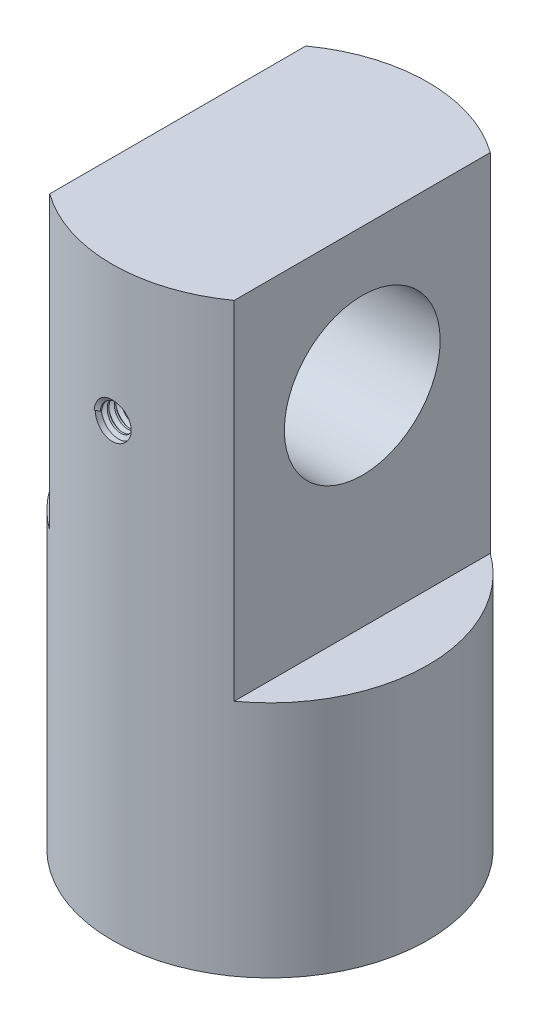
SolidWorks part; units mm, degrees
ref_plane "Front Plane" through (0, 0, 0) normal (0, 0, 1) x (1, 0, 0)
ref_plane "Top Plane" through (0, 0, 0) normal (0, 1, 0) x (1, 0, 0)
ref_plane "Right Plane" through (0, 0, 0) normal (1, 0, 0) x (0, 0, -1)
sketch "Sketch1" plane through (0, 0, 0) normal (0, 1, 0) x (1, 0, 0)
  circle A0 centre (0, 0) radius 22.32
  dimension "D1" = 44.64
extrude "Boss-Extrude1" add sketch "Sketch1" against normal blind 82.8
ref_plane "Plane1" through (0, -82.8, 0) normal (0, -1, 0) x (-1, 0, 0)
sketch "Sketch2" plane through (0, 0, 0) normal (0, 1, 0) x (1, 0, 0)
  line L2 (-13.05, 18.1075) -> (-13.05, -18.1075) construction
  line L4 (13.05, 18.1075) -> (13.05, -18.1075) construction
  circle A0 centre (0, 0) radius 22.32 construction
  arc A1 (-13.05, -18.1075) -> (13.05, -18.1075) centre (0, 0) ccw construction
  arc A2 (-13.05, 18.1075) -> (13.05, 18.1075) centre (0, 0) cw construction
  dimension "D3" = 22.32
  dimension "D4" = 22.32
  dimension "D1" = 26.1
  dimension "D2" = 36.2149
  dimension "D5" = 36.2149
sketch "Sketch3" plane through (0, 0, 0) normal (0, 1, 0) x (1, 0, 0)
  line L0 (-13.05, 18.1075) -> (-13.05, -18.1075)
  arc A0 (-13.05, 18.1075) -> (-13.05, -18.1075) centre (0, 0) ccw
  circle A1 centre (0, 0) radius 22.32 construction
extrude "Cut-Extrude1" cut sketch "Sketch3" against normal blind 41.26
sketch "Sketch4" plane through (0, 0, 0) normal (0, 1, 0) x (1, 0, 0)
  line L0 (13.05, 18.1075) -> (13.05, -18.1075)
  arc A0 (13.05, 18.1075) -> (13.05, -18.1075) centre (0, 0) cw
extrude "Cut-Extrude2" cut sketch "Sketch4" against normal blind 49.1
sketch "Sketch5" plane through (0, 0, 0) normal (1, 0, 0) x (0, 0, -1)
  line L0 (-18.1075, 0) -> (18.1075, 0) construction
  circle A0 centre (0, -19.47) radius 11.02
  dimension "D1" = 22.04
  dimension "D2" = 19.47
extrude "Cut-Extrude3" cut sketch "Sketch5" against normal through all both and the other way through all
sketch "Sketch6" plane through (0, -82.8, 0) normal (0, -1, 0) x (-1, 0, 0)
  circle A0 centre (0, 0) radius 10.15
  dimension "D1" = 20.3
hole_wizard "Ø20.0mm Dowel Hole1" positions "Sketch7" profile "Sketch8" hole size "Ø20.0" standard "ISO"
sketch "Sketch7" plane through (0, -82.8, 0) normal (0, -1, 0) x (-1, 0, 0)
  point P0 (0, 0)
sketch "Sketch8" plane through (0, -82.8, 0) normal (1, 0, 0) x (0, 0, -1)
  line L0 (0, 0) -> (0, 43.7086)
  line L1 (0, 43.7086) -> (10, 37.7)
  line L2 (10, 37.7) -> (10, 0)
  line L5 (10, 0) -> (0, 0)
  line L10 (0, 43.7086) -> (-10, 37.7) construction
  line L11 (0, -6.35) -> (0, 107.95) construction
  dimension "Hole Dia." = 20
  dimension "Hole Depth" = 37.7
  dimension "Drill Angle" = 118
thread "Thread1" pitch 1.5 method extrude profile "Thread Profile1" start angle 0, offset 0, length 0, pitch 1.5, diameter 20
ref_plane "Plane2" through (10, -82.8, 0) normal (0, 0, 1) x (1, 0, 0)
sketch "Thread Profile1" plane through (10, -82.8, 0) normal (0, 0, 1) x (1, 0, 0)
  line L0 (0, 0) -> (0, 1.5) construction
  line L11 (0, 0) -> (0, 1.3125)
  line L12 (0, 1.3125) -> (-0.8119, 0.8437)
  line L13 (-0.8119, 0.8437) -> (-0.8119, 0.4687)
  line L15 (-0.8119, 0.4687) -> (0, 0)
  line L17 (-0.8119, 0.6562) -> (0, 0.6562) construction
  point P2 (0, 0)
  dimension "Pitch" = 1.5
  dimension "Profile_Angle" = 60
  dimension "Profile_Land" = 0.375
  dimension "Profile_Height" = 0.8119
ref_plane "Plane5" through (0, 0, 22.32) normal (0, 0, 1) x (1, 0, 0)
sketch "Sketch15" plane through (0, 0, 22.32) normal (0, 0, 1) x (1, 0, 0)
  line L0 (13.05, 0) -> (-13.05, 0) construction
  circle A0 centre (0, -19.15) radius 2.55
  dimension "D1" = 5.1
  dimension "D2" = 19.15
extrude "Cut-Extrude4" cut sketch "Sketch15" against normal up to surface (11.3046 mm away) up to face at (13.05, -19.47, 11.02)
thread "Thread2" pitch 1 method extrude profile "Thread Profile4" start angle 0, offset 0, length 10, pitch 1, diameter 5.1
ref_plane "Plane6" through (-2.55, -19.15, 22.32) normal (0, -1, 0) x (-1, 0, 0)
sketch "Thread Profile4" plane through (-2.55, -19.15, 22.32) normal (0, -1, 0) x (-1, 0, 0)
  line L0 (0, 0) -> (0, 1) construction
  line L11 (0, 0) -> (0, 0.875)
  line L12 (0, 0.875) -> (-0.5413, 0.5625)
  line L13 (-0.5413, 0.5625) -> (-0.5413, 0.3125)
  line L15 (-0.5413, 0.3125) -> (0, 0)
  line L17 (-0.5413, 0.4375) -> (0, 0.4375) construction
  point P2 (0, 0)
  dimension "Pitch" = 1
  dimension "Profile_Angle" = 60
  dimension "Profile_Land" = 0.25
  dimension "Profile_Height" = 0.5413
